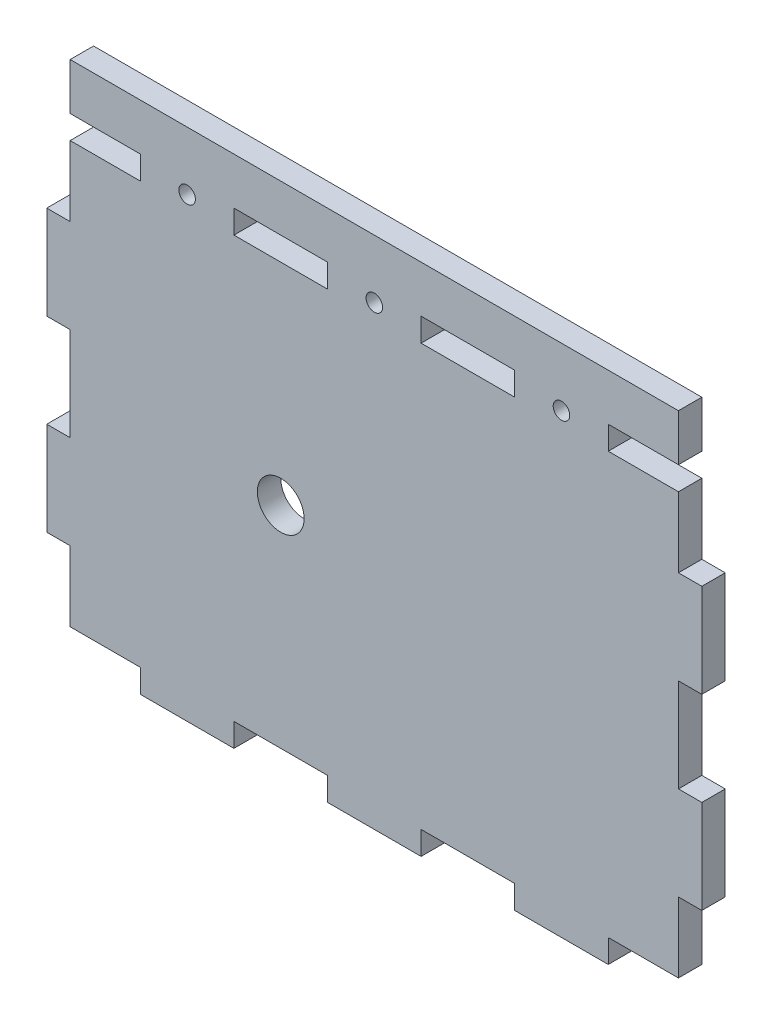
SolidWorks part; units mm, degrees
ref_plane "Front Plane" through (0, 0, 0) normal (0, 0, 1) x (1, 0, 0)
ref_plane "Top Plane" through (0, 0, 0) normal (0, 1, 0) x (1, 0, 0)
ref_plane "Right Plane" through (0, 0, 0) normal (1, 0, 0) x (0, 0, -1)
sketch "Sketch1" plane through (0, 0, 0) normal (0, 0, 1) x (1, 0, 0)
  line L1 (0, 0) -> (177.8, 0)
  line L2 (0, 0) -> (0, 139.7)
  line L3 (0, 139.7) -> (177.8, 139.7)
  line L4 (177.8, 0) -> (177.8, 139.7)
  dimension "D1" = 177.8
  dimension "D2" = 139.7
extrude "Boss-Extrude1" add sketch "Sketch1" along normal blind 6.35
sketch "Sketch5" plane through (0, 0, 6.35) normal (0, 0, 1) x (1, 0, 0)
  line L1 (0, 0) -> (6.35, 0)
  line L2 (0, 0) -> (0, 25.4)
  line L3 (0, 25.4) -> (6.35, 25.4)
  line L4 (6.35, 0) -> (6.35, 25.4)
  dimension "D1" = 25.4
  dimension "D2" = 6.35
extrude "Cut-Extrude4" cut sketch "Sketch5" against normal blind 6.35
sketch "Sketch6" plane through (0, 0, 6.35) normal (0, 0, 1) x (1, 0, 0)
  line L1 (0, 0) -> (25.4, 0)
  line L2 (0, 0) -> (0, 6.35)
  line L3 (0, 6.35) -> (25.4, 6.35)
  line L4 (25.4, 0) -> (25.4, 6.35)
  dimension "D1" = 6.35
  dimension "D2" = 25.4
extrude "Cut-Extrude5" cut sketch "Sketch6" against normal blind 6.35
pattern_linear "LPattern5" count 3 spacing 50.8 along (0, 1, 0) count 2 spacing 171.45 along (1, 0, 0) of "Cut-Extrude4"
pattern_linear "LPattern6" count 4 spacing 50.8 along (1, 0, 0) count 2 spacing 120.65 along (0, 1, 0) of "Cut-Extrude5"
sketch "Sketch7" plane through (0, 0, 6.35) normal (0, 0, 1) x (1, 0, 0)
  line L0 (177.8, 127) -> (152.4, 127) construction
  line L1 (6.35, 120.65) -> (0, 120.65)
  line L2 (6.35, 120.65) -> (6.35, 139.7)
  line L3 (6.35, 139.7) -> (0, 139.7)
  line L4 (0, 120.65) -> (0, 139.7)
  line L5 (177.8, 139.7) -> (171.45, 139.7)
  line L6 (177.8, 139.7) -> (177.8, 127)
  line L7 (177.8, 127) -> (171.45, 127)
  line L8 (171.45, 139.7) -> (171.45, 127)
  dimension "D1" = 6.35
  dimension "D2" = 19.05
  dimension "D3" = 6.35
extrude "Cut-Extrude6" cut sketch "Sketch7" against normal blind 6.35
hole_wizard "#8 Clearance Hole1" positions "Sketch10" profile "Sketch9" hole size "#8" standard "ANSI Inch"
sketch "Sketch10" plane through (0, 0, 6.35) normal (0, 0, 1) x (1, 0, 0)
  line L2 (25.4, 120.65) -> (25.4, 127) construction
  line L3 (76.2, 127) -> (50.8, 127) construction
  line L4 (76.2, 120.65) -> (76.2, 127) construction
  line L5 (127, 120.65) -> (127, 127) construction
  point P0 (38.1, 123.825)
  point P2 (88.9, 123.825)
  point P10 (25.4, 123.825)
  point P18 (139.7, 123.825)
  dimension "D1" = 12.7
  dimension "D2" = 12.7
  dimension "D3" = 12.7
  dimension "D4" = 3.175
sketch "Sketch9" plane through (38.1, 123.825, 6.35) normal (1, 0, 0) x (0, -1, 0)
  line L0 (0, 0) -> (0, 11.5107)
  line L1 (0, 11.5107) -> (2.2479, 10.16)
  line L2 (2.2479, 10.16) -> (2.2479, 0)
  line L5 (2.2479, 0) -> (0, 0)
  line L10 (0, 11.5107) -> (-2.2479, 10.16) construction
  line L11 (0, -6.35) -> (0, 107.95) construction
  dimension "Hole Dia." = 4.4958
  dimension "Hole Depth" = 10.16
  dimension "Drill Angle" = 118
sketch "Sketch11" plane through (0, 0, 6.35) normal (0, 0, 1) x (1, 0, 0)
  circle A0 centre (63.5, 63.5) radius 6.35
  dimension "D1" = 12.7
extrude "Cut-Extrude7" cut sketch "Sketch11" against normal blind 7.62
